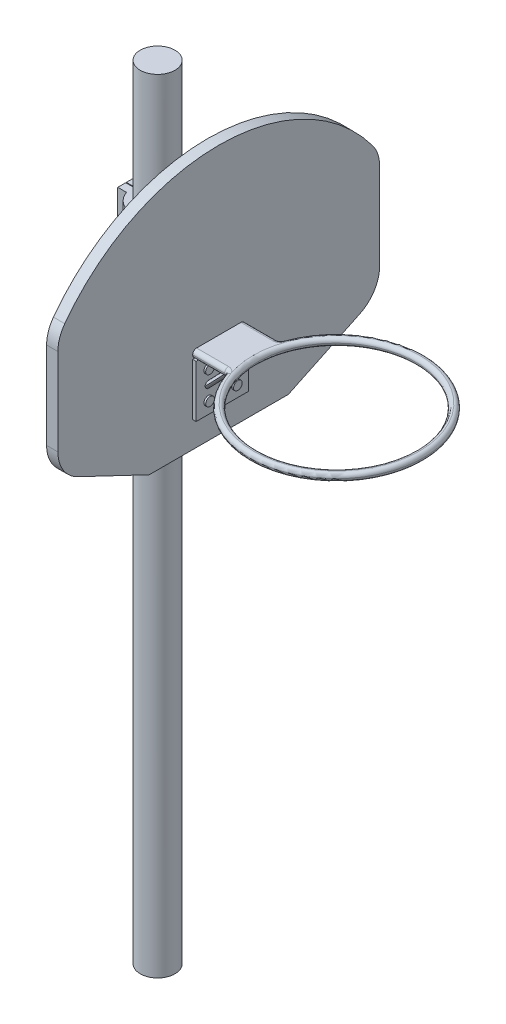
SolidWorks part; units mm, degrees
ref_plane "Front Plane" through (0, 0, 0) normal (0, 0, 1) x (1, 0, 0)
ref_plane "Top Plane" through (0, 0, 0) normal (0, 1, 0) x (1, 0, 0)
ref_plane "Right Plane" through (0, 0, 0) normal (1, 0, 0) x (0, 0, -1)
sketch "Sketch1" plane through (0, 0, 0) normal (0, 1, 0) x (1, 0, 0)
  circle A0 centre (0, 0) radius 12.7
extrude "Boss-Extrude1" add sketch "Sketch1" along normal blind 571.5
ref_plane "Plane1" through (0, 482.6, 0) normal (0, 1, 0) x (1, 0, 0)
sketch "Sketch3" plane through (0, 482.6, 0) normal (0, 1, 0) x (1, 0, 0)
  line L0 (-23.0754, -6.0325) -> (-16.7254, -6.0325)
  line L1 (-23.0754, 6.0325) -> (-16.7254, 6.0325)
  line L2 (29.4254, -6.0325) -> (16.7254, -6.0325)
  line L3 (29.4254, 6.0325) -> (16.7254, 6.0325)
  line L4 (-23.0754, -6.0325) -> (-23.0754, -0.254)
  line L5 (-23.0754, 6.0325) -> (-23.0754, 0.254)
  line L6 (-23.0754, 0.254) -> (-12.6975, 0.254)
  line L7 (-23.0754, -0.254) -> (-12.6975, -0.254)
  line L8 (36.4104, -14.2875) -> (36.4104, -0.254)
  line L9 (36.4104, -0.254) -> (12.6975, -0.254)
  line L10 (36.4104, 14.2875) -> (36.4104, 0.254)
  line L11 (36.4104, 0.254) -> (12.6975, 0.254)
  line L12 (29.4254, -6.0325) -> (29.4254, -14.2875)
  line L13 (29.4254, -14.2875) -> (36.4104, -14.2875)
  line L15 (29.4254, 6.0325) -> (29.4254, 14.2875)
  line L16 (29.4254, 14.2875) -> (36.4104, 14.2875)
  circle A0 centre (0, 0) radius 12.7 construction
  arc A1 (-12.6975, -0.254) -> (12.6975, -0.254) centre (0, 0) ccw
  arc A2 (-16.7254, -6.0325) -> (16.7254, -6.0325) centre (0, 0) ccw
  arc A3 (16.7254, 6.0325) -> (-16.7254, 6.0325) centre (0, 0) ccw
  arc A4 (12.6975, 0.254) -> (-12.6975, 0.254) centre (0, 0) ccw
  point P26 (17.78, 0)
  dimension "D7" = 5.08
  dimension "D1" = 0.254
  dimension "D2" = 0.254
  dimension "D3" = 12.065
  dimension "D4" = 12.7
  dimension "D5" = 6.985
  dimension "D6" = 8.255
  dimension "D8" = 6.35
extrude "Boss-Extrude2" add sketch "Sketch3" against normal blind 38.1
sketch "Sketch4" plane through (36.4104, 0, 0) normal (1, 0, 0) x (0, 0, -1)
  line L0 (-117.475, 468.321) -> (-117.475, 404.821)
  line L1 (117.475, 468.321) -> (117.475, 404.821)
  line L2 (0, 571.5) -> (0, 0) construction
  line L3 (12.7, 571.5) -> (-12.7, 571.5) construction
  line L4 (-102.9953, 381.8884) -> (-50.8, 357.0335)
  line L5 (-50.8, 357.0335) -> (50.8, 357.0335)
  line L6 (50.8, 357.0335) -> (102.9953, 381.8884)
  arc A0 (-112.4782, 483.4494) -> (112.4782, 483.4494) centre (0, 400.05) cw
  arc A1 (-117.475, 468.321) -> (-112.4782, 483.4494) centre (-92.075, 468.321) cw
  arc A2 (117.475, 468.321) -> (112.4782, 483.4494) centre (92.075, 468.321) ccw
  arc A3 (117.475, 404.821) -> (102.9953, 381.8884) centre (92.075, 404.821) cw
  arc A4 (-117.475, 404.821) -> (-102.9953, 381.8884) centre (-92.075, 404.821) ccw
  point P18 (-117.475, 476.25)
  point P21 (117.475, 476.25)
  point P24 (117.475, 388.7835)
  point P27 (-117.475, 388.7835)
  dimension "D1" = 234.95
  dimension "D5" = 25.4
  dimension "D2" = 95.25
  dimension "D3" = 171.45
  dimension "D4" = 31.75
  dimension "D6" = 63.5
  dimension "D7" = 101.6
extrude "Boss-Extrude3" add sketch "Sketch4" along normal blind 8.255
sketch "Sketch5" plane through (44.6654, 0, 0) normal (1, 0, 0) x (0, 0, -1)
  line L0 (0, 540.0743) -> (0, 0) construction
  line L1 (-19.05, 376.0835) -> (19.05, 376.0835)
  line L2 (-19.05, 376.0835) -> (-19.05, 414.1835)
  line L3 (-19.05, 414.1835) -> (19.05, 414.1835)
  line L4 (19.05, 376.0835) -> (19.05, 414.1835)
  line L5 (-19.05, 376.0835) -> (19.05, 414.1835) construction
  line L6 (-19.05, 414.1835) -> (19.05, 376.0835) construction
  line L7 (-50.8, 357.0335) -> (50.8, 357.0335) construction
  arc A0 (112.4782, 483.4494) -> (-112.4782, 483.4494) centre (0, 400.05) ccw construction
  point P0 (0, 395.1335)
  dimension "D1" = 38.1
  dimension "D2" = 38.1
extrude "Boss-Extrude4" add sketch "Sketch5" along normal blind 2.54
sketch "Sketch6" plane through (47.2054, 0, 0) normal (1, 0, 0) x (0, 0, -1)
  line L10 (-10.16, 405.2935) -> (10.16, 384.9735) construction
  line L11 (10.16, 405.2935) -> (-10.16, 384.9735) construction
  line L12 (0, 414.1835) -> (0, 376.0835) construction
  line L13 (19.05, 414.1835) -> (-19.05, 414.1835) construction
  line L14 (-19.05, 376.0835) -> (19.05, 376.0835) construction
  circle A0 centre (-10.16, 405.2935) radius 3.175
  circle A1 centre (10.16, 405.2935) radius 3.175
  circle A2 centre (-10.16, 384.9735) radius 3.175
  circle A3 centre (10.16, 384.9735) radius 3.175
  point P0 (0, 395.1335)
  dimension "D1" = 10.16
  dimension "D2" = 6.35
  dimension "D3" = 10.16
extrude "Boss-Extrude5" add sketch "Sketch6" along normal blind 1.27
sketch "Sketch7" plane through (0, 414.1835, 0) normal (0, 1, 0) x (1, 0, 0)
  line L1 (44.6654, -19.05) -> (70.0654, -19.05)
  line L2 (44.6654, -19.05) -> (44.6654, 19.05)
  line L3 (44.6654, 19.05) -> (70.0654, 19.05)
  arc A2 (70.0654, -19.05) -> (70.0654, 19.05) centre (130.6405, 0) ccw
  circle A3 centre (130.6405, 0) radius 57.785
  circle A4 centre (130.6405, 0) radius 63.5 construction
  point P5 (44.6654, 19.05)
  point P11 (44.6654, 14.8355)
  dimension "D2" = 127
  dimension "D3" = 5.715
  dimension "D1" = 25.4
extrude "Boss-Extrude7" add sketch "Sketch7" along normal blind 5.715 separate body
fillet "Fillet2" radius 2.8575 8 edges at (57.3654, 419.8985, 19.05) (57.3654, 414.1835, 19.05) (57.3654, 419.8985, -19.05) (57.3654, 414.1835, -19.05) (130.6405, 414.1835, 57.785) (130.6405, 419.8985, 57.785) (194.1405, 419.8985, 0) (194.1405, 414.1835, 0)
ref_plane "Plane2" through (0, 0, -10.16) normal (0, 0, -1) x (-1, 0, 0)
sketch "Sketch8" plane through (0, 0, -10.16) normal (0, 0, -1) x (-1, 0, 0)
  line L0 (-68.0036, 414.1835) -> (-47.2054, 392.5935)
  line L1 (-44.6654, 414.1835) -> (-68.0036, 414.1835) construction
  line L2 (-47.2054, 376.0835) -> (-47.2054, 414.1835) construction
  line L3 (-47.2054, 392.5935) -> (-47.2054, 397.6735)
  line L4 (-47.2054, 397.6735) -> (-63.1099, 414.1835)
  line L5 (-63.1099, 414.1835) -> (-68.0036, 414.1835)
  dimension "D1" = 4.445
  dimension "D2" = 5.08
extrude "Boss-Extrude8" add sketch "Sketch8" along normal blind 2.54 and the other way blind 2.54
fillet "Fillet3" radius 2.54 4 edges at (55.1576, 405.9285, -7.62) (55.1576, 405.9285, -12.7) (57.6045, 403.3885, -12.7) (57.6045, 403.3885, -7.62)
ref_plane "Plane3" through (0, 0, 0) normal (0, 0, -1) x (-1, 0, 0)
mirror "Mirror1" about plane through (0, 0, 0) normal (0, 0, -1) of "Boss-Extrude8", "Fillet3"
